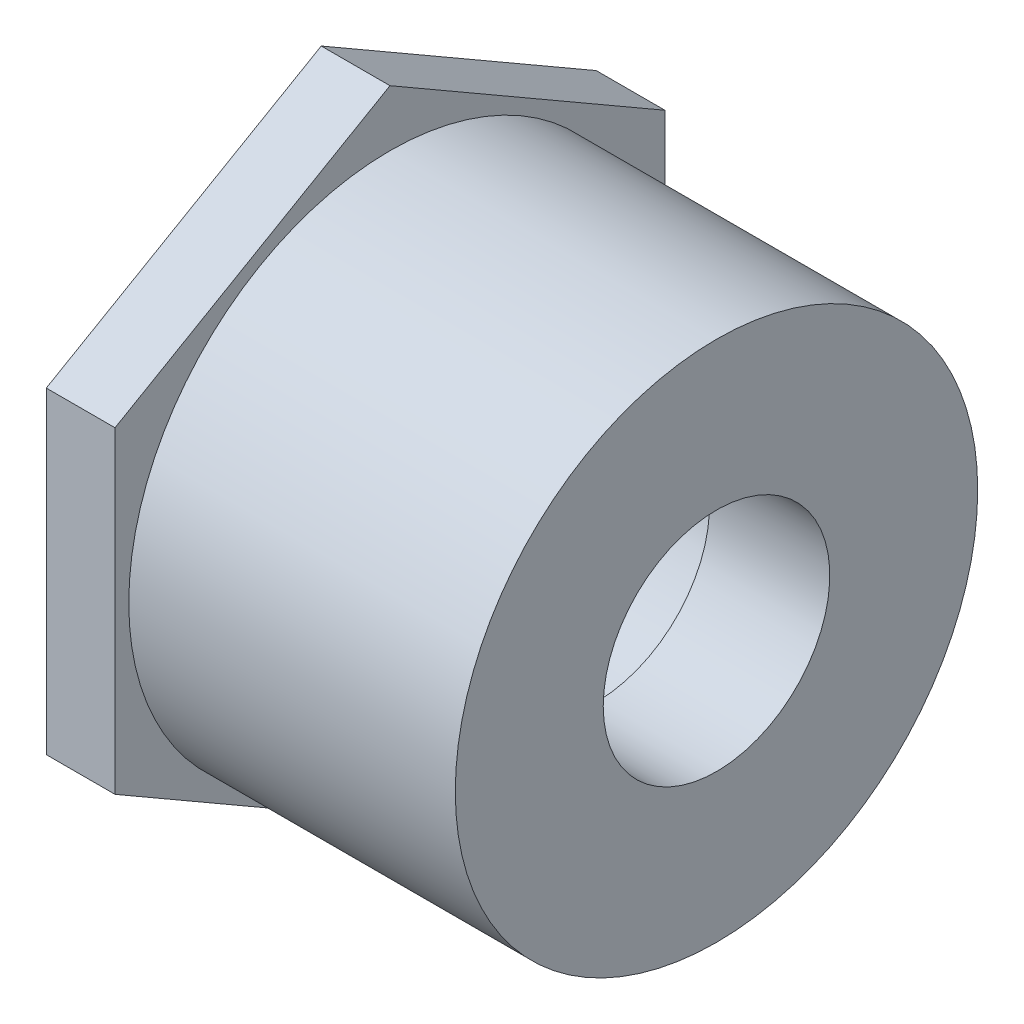
SolidWorks part; units mm, degrees
ref_plane "Front Plane" through (0, 0, 0) normal (0, 0, 1) x (1, 0, 0)
ref_plane "Top Plane" through (0, 0, 0) normal (0, 1, 0) x (1, 0, 0)
ref_plane "Right Plane" through (0, 0, 0) normal (1, 0, 0) x (0, 0, -1)
sketch "Sketch0" plane through (0, 0, 0) normal (0, 0, 1) x (1, 0, 0)
  line L0 (-36.5125, 0) -> (0, 0) construction
  line L2 (-27.7876, 24.13) -> (-27.7876, -24.13) construction
  line L3 (-30.1625, 25.4) -> (-30.1625, -25.4) construction
  line L5 (-11.1125, 13.2842) -> (-36.5125, 13.4366) construction
  line L6 (-11.1125, 13.2842) -> (-11.1125, -13.2842) construction
  line L7 (-11.1125, -13.2842) -> (-36.5125, -13.4366) construction
  line L8 (-36.5125, 13.4366) -> (-36.5125, -13.4366) construction
  line L14 (-11.1125, 10.4648) -> (-11.1125, -10.4648) construction
  line L21 (-36.5125, 0) -> (-11.1125, 0) construction
  point P12 (-27.7876, 0)
  point P27 (-30.1625, 0)
  dimension "A" = 36.5125
  dimension "OD A 2" = 26.8732
  dimension "OD B 2" = 26.5684
  dimension "ID 2" = 20.9296
  dimension "B" = 11.1125
  dimension "Pipe OD 1" = 48.26
  dimension "C 1" = 27.7876
  dimension "J" = 50.8
  dimension "K" = 6.35
sketch "Sketch1" plane through (0, 0, 0) normal (0, 0, 1) x (1, 0, 0)
  line L0 (-36.5125, 0) -> (0, 0) construction
  line L1 (-36.5125, 0) -> (0, 0) construction
  line L2 (-36.5125, -24.13) -> (0, -24.13)
  line L3 (0, -10.4648) -> (0, -24.13)
  line L4 (-36.5125, -24.13) -> (-36.5125, -13.4366)
  line L5 (-36.5125, -13.4366) -> (-11.1125, -13.2842)
  line L6 (0, 0) -> (0, -10.4648) construction
  line L8 (-11.1125, -10.4648) -> (-11.1125, -13.2842)
  line L11 (-11.1125, -10.4648) -> (0, -10.4648)
revolve "Revolve1" add sketch "Sketch1" angle 360 about L1
sketch "Sketch2" plane through (-36.5125, 0, 0) normal (-1, 0, 0) x (0, 0, 1)
  line L0 (0, 0) -> (0, 29.3294) construction
  line L1 (0, 29.3294) -> (-25.4, 14.6647)
  line L2 (-25.4, 14.6647) -> (-25.4, -14.6647)
  line L3 (-25.4, -14.6647) -> (0, -29.3294)
  line L4 (0, -29.3294) -> (25.4, -14.6647)
  line L5 (25.4, -14.6647) -> (25.4, 14.6647)
  line L6 (25.4, 14.6647) -> (0, 29.3294)
  circle A0 centre (0, 0) radius 13.4366 construction
  circle A1 centre (0, 0) radius 13.4366
  circle A2 centre (0, 0) radius 25.4 construction
  point P3 (0, 25.4)
extrude "Boss-Extrude1" add sketch "Sketch2" against normal up to vertex (6.35 mm away) up to point (-30.1625, 0, 0)
other "CPoint1" parameters "Diameter"=38.1, "StubLength"=57.15
ref_axis "Axis1" through (-21.1125, 0, 0) along (1, 0, 0)
other "CPoint2" parameters "Diameter"=19.05, "StubLength"=57.15
ref_axis "Axis2" through (-1.1125, 0, 0) along (-1, 0, 0)
other "RPoint1"
